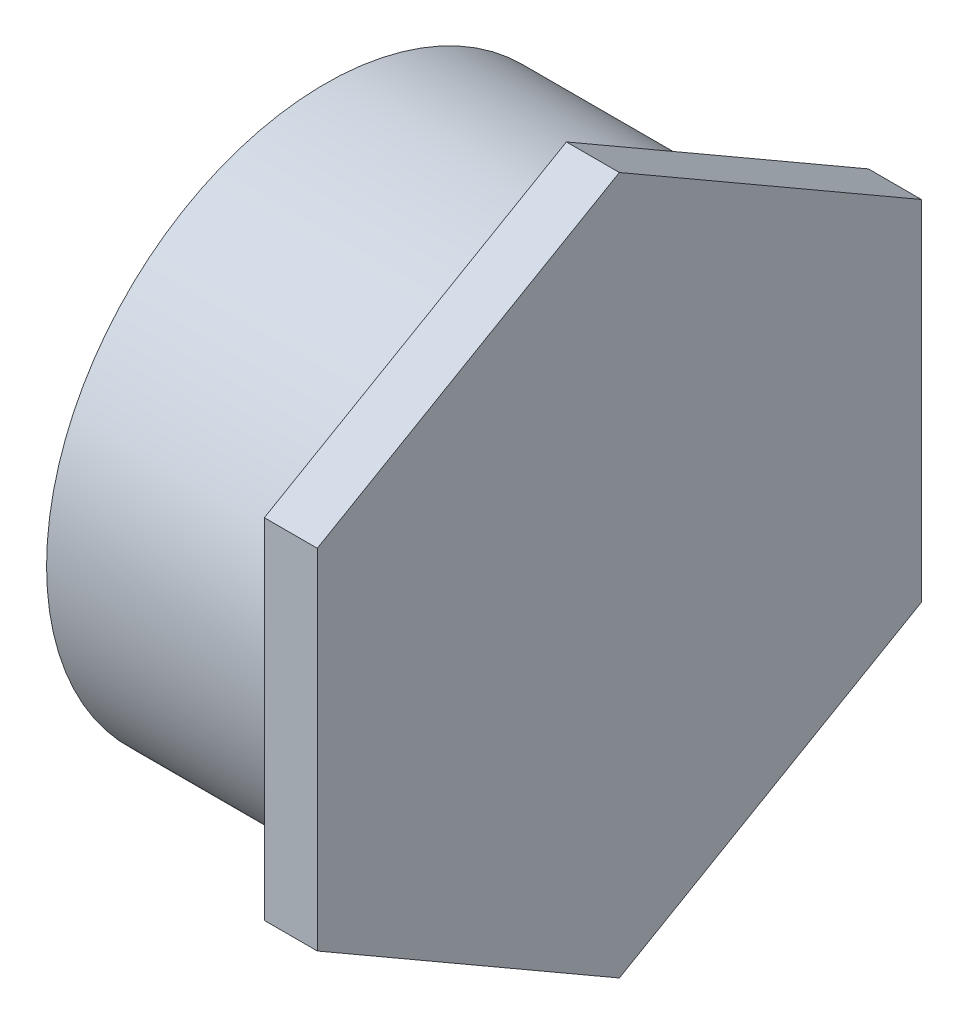
SolidWorks part; units mm, degrees
ref_plane "Front Plane" through (0, 0, 0) normal (0, 0, 1) x (1, 0, 0)
ref_plane "Top Plane" through (0, 0, 0) normal (0, 1, 0) x (1, 0, 0)
ref_plane "Right Plane" through (0, 0, 0) normal (1, 0, 0) x (0, 0, -1)
sketch "Sketch0" plane through (0, 0, 0) normal (0, 0, 1) x (1, 0, 0)
  line L2 (-44.45, 84.1375) -> (-44.45, -84.1375) construction
  line L3 (-44.45, 0) -> (44.45, 0) construction
  line L14 (28.448, 77.0255) -> (28.448, -77.0255) construction
  point P5 (28.448, 0)
  dimension "R" = 16.002
sketch "Sketch1" plane through (0, 0, 0) normal (0, 0, 1) x (1, 0, 0)
  line L0 (-44.45, -84.1375) -> (28.448, -84.1375)
  line L1 (-44.45, 0) -> (44.45, 0) construction
  line L3 (44.45, 0) -> (28.448, 0)
  line L4 (28.448, -77.0255) -> (-44.45, -77.0255)
  line L5 (-44.45, -77.0255) -> (-44.45, -84.1375)
  line L6 (-44.45, 84.1375) -> (-44.45, -84.1375) construction
  line L7 (44.45, 0) -> (44.45, -91.2495)
  line L8 (44.45, -91.2495) -> (28.448, -91.2495)
  line L9 (28.448, -91.2495) -> (28.448, -84.1375)
  line L10 (28.448, 0) -> (28.448, -77.0255)
revolve "Revolve1" add sketch "Sketch1" angle 360 about L1
sketch "Sketch2" plane through (28.448, 0, 0) normal (-1, 0, 0) x (0, 0, 1)
  line L1 (-91.2495, 52.6829) -> (-91.2495, -52.6829)
  line L2 (-91.2495, -52.6829) -> (0, -105.3658)
  line L3 (0, -105.3658) -> (91.2495, -52.6829)
  line L4 (91.2495, -52.6829) -> (91.2495, 52.6829)
  line L5 (91.2495, 52.6829) -> (0, 105.3658)
  line L6 (0, 105.3658) -> (-91.2495, 52.6829)
  circle A0 centre (0, 0) radius 91.2495 construction
  circle A3 centre (0, 0) radius 91.2495 construction
extrude "Boss-Extrude1" add sketch "Sketch2" against normal up to surface (16.002 mm away) up to face at (44.45, 0, 91.2495)
ref_axis "Axis of Rotation" through (28.448, 0, 0) along (-1, 0, 0)
other "CPoint1" parameters "Diameter"=152.4, "StubLength"=152.4
ref_axis "Axis2" through (18.448, 0, 0) along (1, 0, 0)
other "RPoint1"
equation "\"R@Sketch0\" = \"Wall Thickness@Sketch0\"*2.250"
